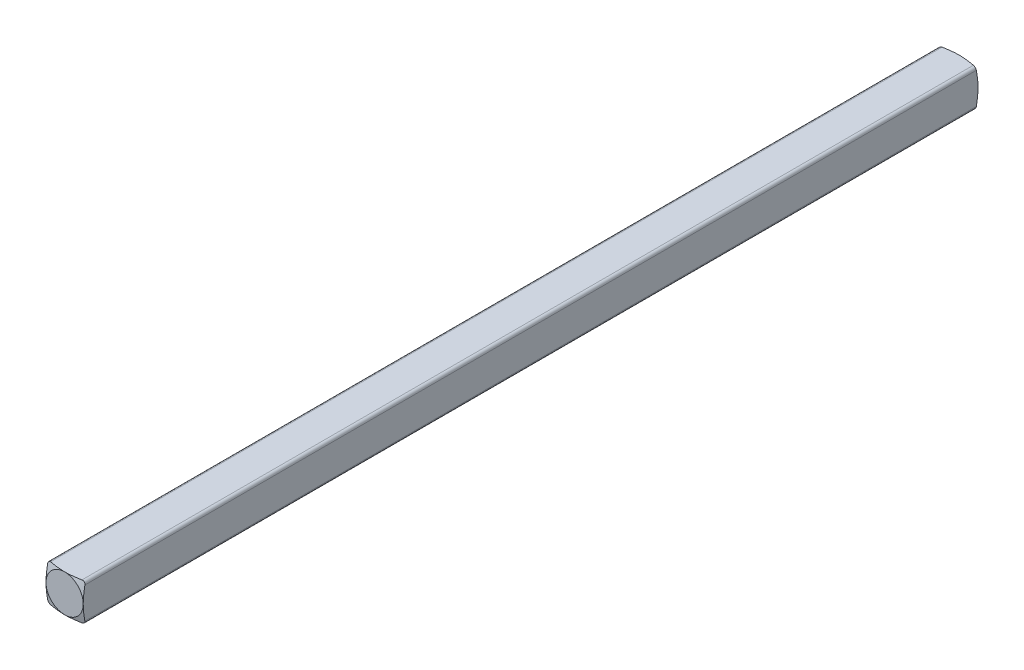
SolidWorks part; units mm, degrees
material "Plain Carbon Steel"
ref_plane "Front Plane" through (0, 0, 0) normal (0, 0, 1) x (1, 0, 0)
ref_plane "Top Plane" through (0, 0, 0) normal (0, 1, 0) x (1, 0, 0)
ref_plane "Right Plane" through (0, 0, 0) normal (1, 0, 0) x (0, 0, -1)
sketch "Sketch1" plane through (0, 0, 0) normal (0, 0, 1) x (1, 0, 0)
  line L0 (0.0501, 1.585) -> (0.0501, -1.585) construction
  line L1 (-1.5349, -1.585) -> (1.6351, -1.585)
  line L2 (-1.5349, -1.585) -> (-1.5349, 1.585)
  line L3 (-1.5349, 1.585) -> (1.6351, 1.585)
  line L4 (1.6351, -1.585) -> (1.6351, 1.585)
  line L5 (1.6351, 0) -> (-1.5349, 0) construction
  dimension "D1" = 3.17
  dimension "D2" = 3.17
  dimension "D3" = 1.6351
extrude "Extrude1" add sketch "Sketch1" along normal mid plane 76.2
sketch "Sketch4" plane through (0, 0, 0) normal (0, -1, 0) x (1, 0, 0)
  line L0 (1.6351, 38.1) -> (2.5551, 38.1)
  line L2 (2.5551, 38.1) -> (2.5551, 37.83)
  line L5 (0.0501, -38.1) -> (0.0501, 2.4929) construction
  line L6 (-1.5349, -38.1) -> (1.6351, -38.1) construction
  line L7 (1.6351, 11.0508) -> (1.6351, 10.1958) construction
  line L8 (2.5551, 37.83) -> (1.6351, 38.1)
  dimension "D1" = 0.27
  dimension "D2" = 0.9588
revolve "Cut-Revolve3" cut sketch "Sketch4" angle 360 about L5
mirror "Mirror2" about plane through (0, 0, 0) normal (0, 0, 1) of "Cut-Revolve3"
fillet "Fillet1" radius 0.25 4 edges at (1.6351, 1.585, 0) (1.6351, -1.585, 0) (-1.5349, -1.585, 0) (-1.5349, 1.585, 0)
ref_axis "Axis1" through (0.0501, 0, 41.818) along (0, 0, -1)
ref_plane "Plane1" through (0, 0, 1.83) normal (0, 0, 1) x (1, 0, 0)
ref_plane "Plane2" through (0, 0, 9.35) normal (0, 0, 1) x (1, 0, 0)
ref_plane "Plane3" through (0, 0, 20.76) normal (0, 0, -1) x (-1, 0, 0)
ref_plane "Plane4" through (0, 0, 31.33) normal (0, 0, 1) x (1, 0, 0)
ref_plane "Plane5" through (0, 0, -19.76) normal (0, 0, -1) x (-1, 0, 0)
ref_plane "Plane6" through (0, 0, 19.06) normal (0, 0, 1) x (1, 0, 0)
ref_plane "Plane7" through (0, 0, -5.8) normal (0, 0, -1) x (-1, 0, 0)
ref_plane "Plane8" through (0, 0, -20.07) normal (0, 0, -1) x (-1, 0, 0)
ref_plane "Plane9" through (0, 0, 6.9) normal (0, 0, -1) x (-1, 0, 0)
ref_plane "Plane10" through (0, 0, -28.07) normal (0, 0, -1) x (-1, 0, 0)
ref_plane "Plane11" through (0, 0, -22.81) normal (0, 0, -1) x (-1, 0, 0)
ref_plane "Plane12" through (0, 0, 25.56) normal (0, 0, 1) x (1, 0, 0)
